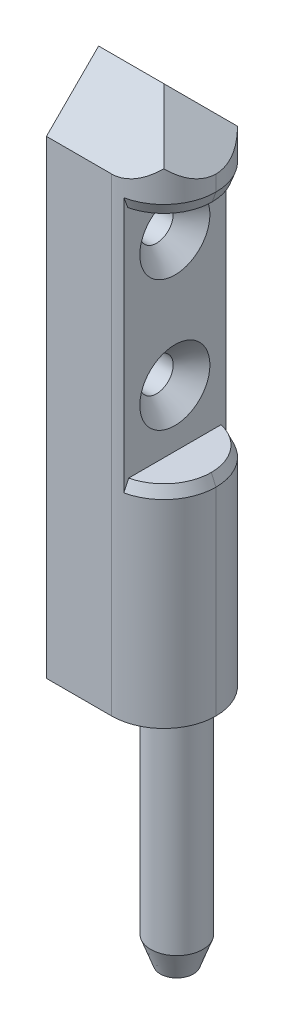
SolidWorks part; units mm, degrees
material "AISI 316 Arkusz stali nierdzewnej (SS)"
ref_plane "Płaszczyzna przednia" through (0, 0, 0) normal (0, 0, 1) x (1, 0, 0)
ref_plane "Płaszczyzna górna" through (0, 0, 0) normal (0, 1, 0) x (1, 0, 0)
ref_plane "Płaszczyzna prawa" through (0, 0, 0) normal (1, 0, 0) x (0, 0, -1)
sketch "Szkic2" plane through (0, 0, 0) normal (0, 1, 0) x (1, 0, 0)
  line L0 (2.12, 10) -> (22.5, 10)
  line L1 (2.12, -10) -> (22.5, -10)
  line L2 (22.5, 10) -> (22.5, -10)
  line L3 (0, 13.3006) -> (0, -13.3006) construction
  line L6 (2.12, -10) -> (0, -10)
  line L7 (0, -10) -> (0, 10)
  line L8 (0, 10) -> (2.12, 10)
  point P0 (0, 0)
  point P11 (0, 0)
  dimension "D1" = 22.5
  dimension "D7" = 10
  dimension "D2" = 20
  dimension "D4" = 20
extrude "Dodanie-wyciągnięcie1" add sketch "Szkic2" along normal blind 100
chamfer "Sfazowanie1" distance 10 angle 45 3 edges at (11.25, 100, -10) (22.5, 100, 0) (11.25, 100, 10)
fillet "Zaokrąglenie1" radius 10 2 edges at (22.5, 45, -10) (22.5, 45, 10)
ref_plane "Płaszczyzna1" through (14.62, 0, 0) normal (1, 0, 0) x (0, 0, -1)
sketch "Szkic3" plane through (14.62, 0, 0) normal (1, 0, 0) x (0, 0, -1)
  line L0 (-10, 85) -> (10, 85)
  line L1 (10, 90) -> (10, 0) construction
  line L3 (10, 85) -> (10, 40)
  line L4 (10, 40) -> (-10, 40)
  line L5 (-10, 40) -> (-10, 85)
  line L6 (-10, 0) -> (0, 0) construction
  point P6 (0, 0)
  point P9 (0, 0)
  dimension "D4" = 40
  dimension "D5" = 20
  dimension "D6" = 15
  dimension "D1" = 20
  dimension "D2" = 20
  dimension "D3" = 45
extrude "Wytnij-wyciągnięcie1" cut sketch "Szkic3" along normal blind 100 contours L5 L0 L3 L4
chamfer "Sfazowanie2" distance 2 angle 24 2 edges at (20.2846, 40, -6.2769) (20.2846, 40, 6.2769) first distance on face at (18.9251, 57.9469, -5.8293) first distance on face at (18.9251, 57.9469, 5.8293)
chamfer "Sfazowanie3" distance 2 angle 20 2 edges at (20.2846, 85, 6.2769) (20.2846, 85, -6.2769) first distance on face at (18.9251, 57.5025, 5.8293) first distance on face at (18.9251, 57.5025, -5.8293)
sketch "Szkic5" plane through (14.62, 0, 0) normal (1, 0, 0) x (0, 0, -1)
  line L0 (-10, 85) -> (10, 85)
  line L1 (10, 85) -> (10, 40)
  line L2 (10, 40) -> (-10, 40)
  line L3 (-10, 40) -> (-10, 85)
  line L4 (-10, 76) -> (10, 76) construction
  line L5 (0, 85) -> (0, 40) construction
  line L6 (-10, 51) -> (10, 51) construction
  point P14 (0, 76)
  point P17 (0, 51)
  dimension "D1" = 9
  dimension "D2" = 25
  dimension "D3" = 11
hole_wizard "Pogłębienie stożkowe pod M6 Wkręt z łbem stożkowym płaskim2" positions "Szkic5" profile "Szkic6" countersink size "M6" standard "ISO"
sketch "Szkic6" plane through (14.62, 51, 0) normal (0, 1, 0) x (0, 0, -1)
  line L0 (0, 0) -> (0, 41.9228)
  line L1 (0, 41.9228) -> (3.2, 40)
  line L2 (3.2, 40) -> (3.2, 3.52)
  line L3 (3.2, 3.52) -> (6.72, 0)
  line L5 (6.72, 0) -> (0, 0)
  line L6 (-3.2, 3.52) -> (-6.72, 0) construction
  line L10 (0, 41.9228) -> (-3.2, 40) construction
  line L11 (0, -6.35) -> (0, 107.95) construction
  dimension "Średnica otworu" = 6.4
  dimension "Głębokośc otworu" = 40
  dimension "Średnica zewnętrznego pogłębienia stożkowego" = 13.44
  dimension "Kąt zewnętrznego pogłębienia stożkowego" = 90
  dimension "Kąt wiertła" = 118
sketch "Szkic7" plane through (0, 0, 0) normal (0, -1, 0) x (1, 0, 0)
  line L0 (12.5, -10) -> (0, -10) construction
  circle A0 centre (15, 0) radius 5
  dimension "D1" = 10
  dimension "D2" = 15
  dimension "D3" = 10
extrude "Dodanie-wyciągnięcie2" add sketch "Szkic7" along normal blind 45
chamfer "Sfazowanie5" distance 5 angle 20 1 edges at (15, -45, -5) first distance on face at (15, -45, -5)
